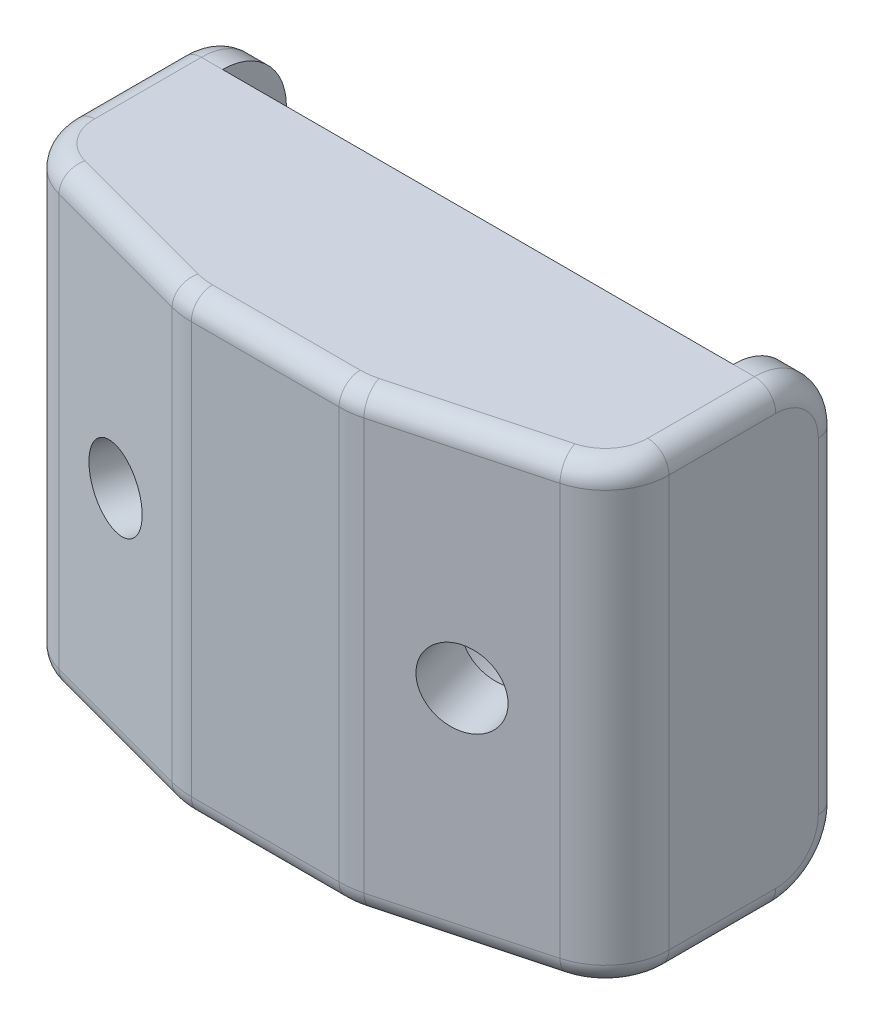
SolidWorks part; units mm, degrees
material "PET"
ref_plane "Front Plane" through (0, 0, 0) normal (0, 0, 1) x (1, 0, 0)
ref_plane "Top Plane" through (0, 0, 0) normal (0, 1, 0) x (1, 0, 0)
ref_plane "Right Plane" through (0, 0, 0) normal (1, 0, 0) x (0, 0, -1)
sketch "Sketch1" plane through (0, 0, 0) normal (0, 0, 1) x (1, 0, 0)
  line L8 (101.7795, 4.4787) -> (146.2295, 4.4787)
  line L9 (146.2295, 4.4787) -> (146.2295, 38.3463)
  line L10 (146.2295, 38.3463) -> (101.7795, 38.3463)
  line L11 (101.7795, 38.3463) -> (101.7795, 4.4787)
  line L20 (143.0545, 5.1137) -> (143.0545, 37.7113)
  line L21 (143.0545, 37.7113) -> (104.9545, 37.7113)
  line L22 (104.9545, 37.7113) -> (104.9545, 5.1137)
  line L23 (104.9545, 5.1137) -> (143.0545, 5.1137)
  dimension "D1" = 33.8676
  dimension "D2" = 44.45
  dimension "D3" = 3.175
  dimension "D4" = 3.175
extrude "Boss-Extrude1" add sketch "Sketch1" against normal blind 6.35
sketch "Sketch2" plane through (0, 0, 0) normal (0, 0, 1) x (1, 0, 0)
  line L4 (101.7795, 38.3463) -> (101.7795, 4.4787)
  line L5 (101.7795, 4.4787) -> (146.2295, 4.4787)
  line L6 (146.2295, 4.4787) -> (146.2295, 38.3463)
  line L7 (146.2295, 38.3463) -> (101.7795, 38.3463)
  line L8 (101.7795, 38.3463) -> (101.7795, 4.4787)
  line L9 (101.7795, 4.4787) -> (146.2295, 4.4787)
  line L10 (146.2295, 4.4787) -> (146.2295, 38.3463)
  line L11 (146.2295, 38.3463) -> (101.7795, 38.3463)
  dimension "D1" = 0
extrude "Boss-Extrude2" add sketch "Sketch2" along normal blind 9.525
sketch "Sketch3" plane through (0, 4.4787, 0) normal (0, -1, 0) x (1, 0, 0)
  line L0 (130.3545, 9.525) -> (146.2295, 5.2713)
  line L1 (101.7795, 9.525) -> (146.2295, 9.525) construction
  line L2 (146.2295, -6.35) -> (146.2295, 9.525) construction
  line L3 (146.2295, 5.2713) -> (146.2295, 9.525)
  line L4 (146.2295, 9.525) -> (130.3545, 9.525)
  line L5 (124.0045, 9.525) -> (124.0045, -6.35) construction
  line L6 (101.7795, -6.35) -> (146.2295, -6.35) construction
  line L7 (101.7795, 9.525) -> (117.6545, 9.525)
  line L8 (101.7795, 5.2713) -> (101.7795, 9.525)
  line L9 (117.6545, 9.525) -> (101.7795, 5.2713)
  dimension "D1" = 15
  dimension "D2" = 12.7
extrude "Cut-Extrude1" cut sketch "Sketch3" against normal through all
sketch "Sketch4" plane through (0, 0, -6.35) normal (0, 0, -1) x (-1, 0, 0)
  line L0 (-146.2295, 38.3463) -> (-101.7795, 38.3463) construction
  line L1 (-146.2295, 4.4787) -> (-143.0545, 4.4787)
  line L2 (-146.2295, 4.4787) -> (-146.2295, 38.3463)
  line L3 (-146.2295, 38.3463) -> (-143.0545, 38.3463)
  line L4 (-143.0545, 4.4787) -> (-143.0545, 38.3463)
  line L5 (-143.0545, 5.1137) -> (-143.0545, 37.7113) construction
  line L6 (-104.9545, 37.7113) -> (-104.9545, 5.1137) construction
  line L7 (-101.7795, 4.4787) -> (-104.9545, 4.4787)
  line L8 (-101.7795, 4.4787) -> (-101.7795, 38.3463)
  line L9 (-101.7795, 38.3463) -> (-104.9545, 38.3463)
  line L10 (-104.9545, 4.4787) -> (-104.9545, 38.3463)
extrude "Boss-Extrude3" add sketch "Sketch4" along normal blind 4.7625
shell "Shell2" thickness 4.7625 removed face at (124.0045, 21.4125, 0)
fillet "Fillet4" radius 4.7625 4 edges at (144.642, 38.3463, -11.1125) (103.367, 38.3463, -11.1125) (144.642, 4.4787, -11.1125) (103.367, 4.4787, -11.1125)
fillet "Fillet1" radius 4.7625 2 edges at (146.2295, 21.4125, 5.2713) (101.7795, 21.4125, 5.2713)
fillet "Fillet3" radius 6.35 2 edges at (117.6545, 21.4125, 9.525) (130.3545, 21.4125, 9.525)
fillet "Fillet2" radius 1.5875 24 edges at (124.0045, 38.3463, 9.525) (111.0781, 38.3463, 7.7629) (102.7636, 38.3463, 4.5161) (101.7795, 38.3463, -2.3665) (146.2295, 38.3463, -2.3665) (145.2453, 38.3463, 4.5161) (136.9308, 38.3463, 7.7629) (101.7795, 4.4787, -2.3665) (102.7636, 4.4787, 4.5161) (111.0781, 4.4787, 7.7629) (124.0045, 4.4787, 9.525) (136.9308, 4.4787, 7.7629) (145.2453, 4.4787, 4.5161) (146.2295, 4.4787, -2.3665) (130.3473, 38.3463, 9.4707) (117.6616, 38.3463, 9.4707) (130.3473, 4.4787, 9.4707) (117.6616, 4.4787, 9.4707) (101.7795, 5.8736, -9.7176) (101.7795, 21.4125, -11.1125) (101.7795, 36.9514, -9.7176) (146.2295, 36.9514, -9.7176) (146.2295, 21.4125, -11.1125) (146.2295, 5.8736, -9.7176)
hole_wizard "#10 Clearance Hole1" positions "Sketch5" profile "Sketch6" hole size "#10" standard "ANSI Inch" end condition up to next
sketch "Sketch5" plane through (5.5001, 0, -20.5267) normal (-0.2588, 0, 0.9659) x (0.9659, 0, 0.2588)
  line L0 (103.3301, 36.7588) -> (115.2747, 6.0662) construction
  point P7 (109.3024, 21.4125)
sketch "Sketch6" plane through (111.0781, 21.4125, 7.7629) normal (0, 1, 0) x (0.9659, 0, 0.2588)
  line L0 (0, 0) -> (0, 7.8021)
  line L1 (0, 7.8021) -> (2.8067, 7.8021)
  line L2 (2.8067, 7.8021) -> (2.8067, 0)
  line L5 (2.8067, 0) -> (0, 0)
  line L11 (0, -6.35) -> (0, 107.95) construction
  dimension "Thru Hole Dia." = 5.6134
  dimension "Thru Hole Depth" = 7.8021
ref_plane "Plane1" through (124.0045, 0, 0) normal (1, 0, 0) x (0, 0, -1)
mirror "Mirror1" about plane through (124.0045, 0, 0) normal (1, 0, 0) of "#10 Clearance Hole1"
ref_plane "Plane2" through (0, 21.4125, 0) normal (0, -1, 0) x (-1, 0, 0)
sketch "Sketch8" plane through (0, 5.1137, 0) normal (0, 1, 0) x (1, 0, 0)
  line L1 (106.542, 0) -> (106.542, -1.6169) construction
  line L2 (106.542, -1.6169) -> (118.2815, -4.7625) construction
  line L3 (118.2815, -4.7625) -> (129.7275, -4.7625) construction
  line L4 (129.7275, -4.7625) -> (141.467, -1.6169) construction
  line L5 (141.467, -1.6169) -> (141.467, 0) construction
  line L6 (104.9545, 0) -> (143.0545, 0) construction
  line L7 (143.0545, 0) -> (143.0545, 6.35) construction
  line L8 (143.0545, 6.35) -> (104.9545, 6.35) construction
  line L9 (104.9545, 6.35) -> (104.9545, 0) construction
  line L11 (106.542, 0) -> (106.542, -1.6169)
  line L12 (106.542, -1.6169) -> (118.2815, -4.7625)
  line L13 (118.2815, -4.7625) -> (129.7275, -4.7625)
  line L14 (129.7275, -4.7625) -> (141.467, -1.6169)
  line L15 (141.467, -1.6169) -> (141.467, 0)
  line L16 (104.9545, 0) -> (106.542, 0)
  line L17 (143.0545, 0) -> (143.0545, 6.35)
  line L18 (143.0545, 6.35) -> (104.9545, 6.35)
  line L19 (104.9545, 6.35) -> (104.9545, 0)
  line L20 (141.467, 0) -> (143.0545, 0)
extrude "Boss-Extrude4" add sketch "Sketch8" along normal up to next
sketch "Sketch9" plane through (5.5001, 0, -20.5267) normal (-0.2588, 0, 0.9659) x (0.9659, 0, 0.2588)
  circle A0 centre (109.3024, 21.4125) radius 5.5562 construction
  circle A1 centre (109.3024, 21.4125) radius 5.5563 construction
  circle A2 centre (109.3024, 21.4125) radius 6.8262
  dimension "D1" = 1.27
extrude "Cut-Extrude2" cut sketch "Sketch9" against normal through all from offset 4.7625 offset against normal yes
mirror "Mirror2" about plane through (124.0045, 0, 0) normal (1, 0, 0) of "Cut-Extrude2"
hole_wizard "Hole1" positions "Sketch11" profile "Sketch12" legacy
sketch "Sketch11" plane through (0, 0, -6.35) normal (0, 0, -1) x (-1, 0, 0)
  line L2 (-124.0045, 21.4125) -> (-124.0045, 4.4787) construction
  line L3 (-104.9545, 4.4787) -> (-143.0545, 4.4787) construction
  line L4 (-114.8597, 21.4125) -> (-133.1492, 21.4125) construction
  ellipse E3 centre (-133.1492, 21.4125) end of major axis (-140.2163, 21.4125) minor radius 6.8262 construction
  ellipse E4 centre (-114.8597, 21.4125) end of major axis (-107.7926, 21.4125) minor radius 6.8262 construction
  point P53 (-124.0045, 11.2525)
  point P55 (-124.0045, 31.5725)
  dimension "D1" = 10.16
sketch "Sketch12" plane through (124.0045, 31.5725, -6.35) normal (1, 0, 0) x (0, 1, 0)
  line L0 (0, 0) -> (0, 7.62)
  line L1 (0, 7.62) -> (4.4323, 7.62)
  line L2 (4.4323, 7.62) -> (4.6101, 0)
  line L3 (4.6101, 0) -> (0, 0)
  line L4 (0, 110) -> (0, -10) construction
  dimension "Minor Diameter" = 8.8646
  dimension "Depth" = 7.62
  dimension "Major Diameter" = 9.2202
hole_wizard "1/4 Clearance Hole1" positions "Sketch13" profile "Sketch14" hole size "1/4" standard "ANSI Inch"
sketch "Sketch13" plane through (0, 0, -6.35) normal (0, 0, -1) x (-1, 0, 0)
  point P0 (-124.0045, 11.2525)
  point P3 (-124.0045, 31.5725)
sketch "Sketch14" plane through (124.0045, 11.2525, -6.35) normal (1, 0, 0) x (0, 1, 0)
  line L0 (0, 0) -> (0, 11.7978)
  line L1 (0, 11.7978) -> (3.5712, 9.652)
  line L2 (3.5712, 9.652) -> (3.5712, 0)
  line L5 (3.5712, 0) -> (0, 0)
  line L10 (0, 11.7978) -> (-3.5712, 9.652) construction
  line L11 (0, -6.35) -> (0, 107.95) construction
  dimension "Hole Dia." = 7.1425
  dimension "Hole Depth" = 9.652
  dimension "Drill Angle" = 118
